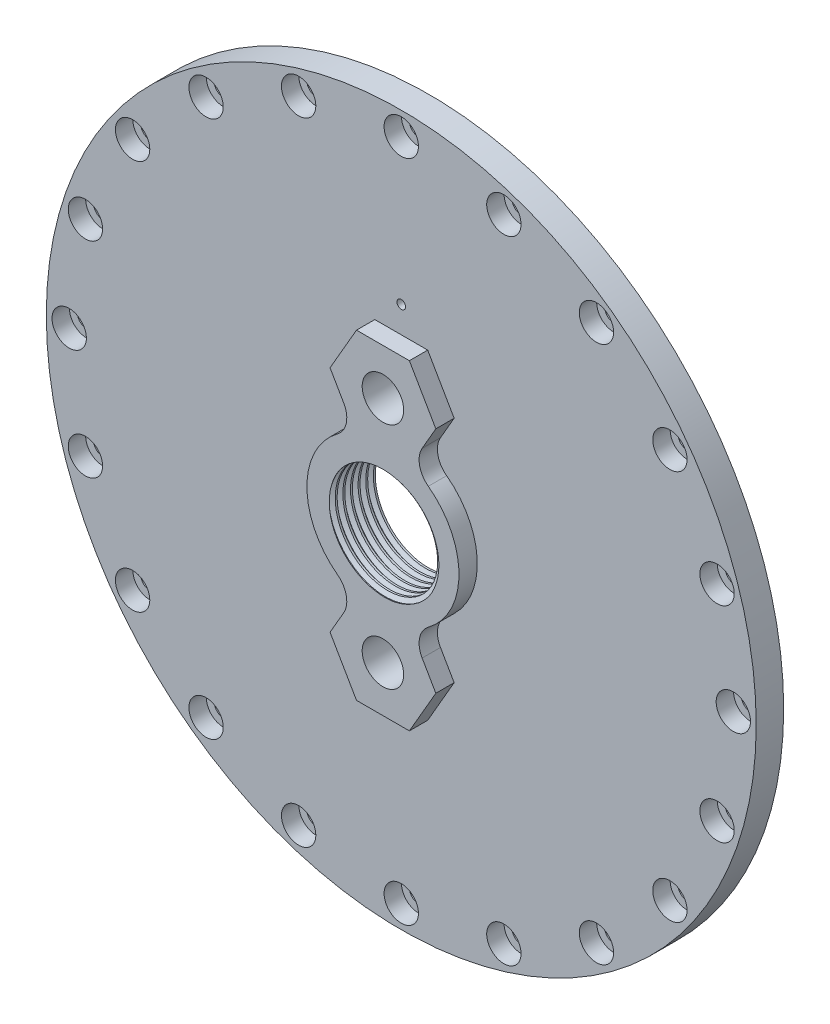
SolidWorks part; units mm, degrees
ref_plane "Front Plane" through (0, 0, 0) normal (0, 0, 1) x (1, 0, 0)
ref_plane "Top Plane" through (0, 0, 0) normal (0, 1, 0) x (1, 0, 0)
ref_plane "Right Plane" through (0, 0, 0) normal (1, 0, 0) x (0, 0, -1)
sketch "Sketch1" plane through (0, 0, 0) normal (1, 0, 0) x (0, 0, -1)
  line L0 (0, 21.082) -> (0, 98.425)
  line L1 (0, 98.425) -> (7.62, 98.425)
  line L2 (7.62, 98.425) -> (7.62, 88.6333)
  line L3 (7.62, 83.82) -> (5.08, 83.82)
  line L4 (5.08, 83.82) -> (5.08, 56.8325)
  line L5 (5.08, 56.8325) -> (7.62, 56.8325)
  line L6 (7.62, 56.8325) -> (7.62, 53.0225)
  line L7 (7.62, 14.732) -> (-5.08, 14.732)
  line L8 (-5.08, 14.732) -> (-5.08, 21.082)
  line L9 (-5.08, 21.082) -> (0, 21.082)
  line L10 (0, 0) -> (59.2702, 0) construction
  line L12 (7.62, 49.6951) -> (6.2992, 49.6951)
  line L14 (7.62, 47.0535) -> (6.2992, 47.0535)
  line L15 (6.2992, 49.6951) -> (6.2992, 47.0535)
  line L20 (7.62, 47.0535) -> (7.62, 46.0375)
  line L21 (7.62, 85.1027) -> (7.62, 83.82)
  line L22 (7.62, 50.4825) -> (7.62, 49.6951)
  line L23 (7.62, 21.59) -> (7.62, 14.732)
  line L24 (7.62, 46.0375) -> (5.08, 46.0375)
  line L26 (7.62, 21.59) -> (5.08, 21.59)
  line L27 (5.08, 46.0375) -> (5.08, 21.59)
  line L28 (7.62, 53.0225) -> (6.35, 53.0225)
  line L32 (7.62, 50.4825) -> (6.35, 50.4825)
  line L33 (6.35, 53.0225) -> (6.35, 50.4825)
  line L35 (7.62, 88.6333) -> (5.6642, 88.6333)
  line L37 (7.62, 85.1027) -> (5.6642, 85.1027)
  line L38 (5.6642, 88.6333) -> (5.6642, 85.1027)
  point P19 (6.35, 51.7525)
  point P22 (6.2992, 48.3743)
  point P31 (5.6642, 86.868)
  dimension "D1" = 196.85
  dimension "D2" = 2.54
  dimension "D3" = 7.62
  dimension "D4" = 2.54
  dimension "D5" = 113.665
  dimension "D6" = 12.7
  dimension "D7" = 29.464
  dimension "D8" = 6.35
  dimension "D9" = 2.6416
  dimension "D10" = 96.7486
  dimension "D11" = 1.3208
  dimension "D12" = 167.64
  dimension "D13" = 92.075
  dimension "D14" = 43.18
  dimension "D15" = 1.27
  dimension "D16" = 2.54
  dimension "D17" = 103.505
  dimension "D18" = 1.9558
  dimension "D19" = 3.5306
  dimension "D20" = 173.736
revolve "Revolve1" add sketch "Sketch1" angle 360 about L10 region at (0, 54.7882, -2.7116)
thread "Thread1" pitch 2.1167 method cut profile "Thread Profile1" start angle 0, offset 4.318, length 0, pitch 2.1167, diameter 29.464
ref_plane "Plane1" through (-14.732, 0, 9.398) normal (0, -1, 0) x (-1, 0, 0)
sketch "Thread Profile1" plane through (-14.732, 0, 9.398) normal (0, -1, 0) x (-1, 0, 0)
  line L0 (0, 0) -> (0, 2.1167) construction
  line L1 (0, 0) -> (1.1457, 0.6615)
  line L2 (1.1457, 0.6615) -> (1.1457, 0.926)
  line L3 (1.1457, 0.926) -> (0, 1.5875)
  line L4 (1.1457, 0.7937) -> (0, 0.7937) construction
  line L11 (0, 0) -> (0, 1.5875)
  point P2 (0, 0)
  dimension "Pitch" = 2.1167
  dimension "Profile_Angle" = 60
  dimension "Profile_Land" = 0.2646
  dimension "Profile_Height" = 1.1457
sketch "Sketch15" plane through (0, 0, 0) normal (0, 0, 1) x (1, 0, 0)
  line L10 (0, 0) -> (104.8126, 0) construction
  line L11 (7.3323, 19.05) -> (14.6647, 31.75)
  line L12 (14.6647, 31.75) -> (7.3323, 44.45)
  line L13 (7.3323, 44.45) -> (-7.3323, 44.45)
  line L14 (-7.3323, 44.45) -> (-14.6647, 31.75)
  line L15 (-14.6647, 31.75) -> (-7.3323, 19.05)
  line L16 (-7.3323, 19.05) -> (7.3323, 19.05)
  line L17 (-7.3323, -19.05) -> (7.3323, -19.05)
  line L18 (-14.6647, -31.75) -> (-7.3323, -19.05)
  line L19 (-7.3323, -44.45) -> (-14.6647, -31.75)
  line L20 (7.3323, -44.45) -> (-7.3323, -44.45)
  line L21 (14.6647, -31.75) -> (7.3323, -44.45)
  line L22 (7.3323, -19.05) -> (14.6647, -31.75)
  circle A8 centre (0, 31.75) radius 12.7 construction
  circle A9 centre (0, -31.75) radius 12.7 construction
  dimension "D2" = 63.5
  dimension "D1" = 25.4
extrude "Boss-Extrude1" add sketch "Sketch15" along normal up to surface (5.08 mm away) up to face at (21.082, 0, 5.08)
hole_wizard "1/2-20 Tapped Hole2" positions "Sketch20" profile "Sketch17" tap size "1/2-20" standard "ANSI Inch" end condition through all
sketch "Sketch20" plane through (0, 0, 5.08) normal (0, 0, 1) x (1, 0, 0)
  point P9 (0, 31.75)
  point P16 (0, -31.75)
sketch "Sketch17" plane through (0, 31.75, 5.08) normal (1, 0, 0) x (0, -1, 0)
  line L0 (0, 0) -> (0, 13.4424)
  line L1 (0, 13.4424) -> (5.7544, 13.4424)
  line L2 (5.7544, 13.4424) -> (5.7544, 0)
  line L5 (5.7544, 0) -> (0, 0)
  line L11 (0, -6.35) -> (0, 107.95) construction
  dimension "Thru Tap Drill Dia." = 11.5087
  dimension "Thru Tap Drill Depth" = 13.4424
cosmetic thread "Hole Thread3"
cosmetic thread "Hole Thread4"
hole_wizard "CBORE for #10 Socket Head Cap Screw1" positions "Sketch19" profile "Sketch9" counterbore size "#10" standard "ANSI Inch" end condition up to next
sketch "Sketch19" plane through (0, 0, 0) normal (0, 0, 1) x (1, 0, 0)
  circle A0 centre (0, 0) radius 92.075 construction
  point P0 (0, 92.075)
  point P16 (28.4527, 87.5685)
  point P17 (54.1203, 74.4902)
  point P18 (74.4902, 54.1203)
  point P19 (87.5685, 28.4527)
  point P20 (92.075, 0)
  point P21 (87.5685, -28.4527)
  point P22 (74.4902, -54.1203)
  point P23 (54.1203, -74.4902)
  point P24 (28.4527, -87.5685)
  point P25 (0, -92.075)
  point P26 (-28.4527, -87.5685)
  point P27 (-54.1203, -74.4902)
  point P28 (-74.4902, -54.1203)
  point P29 (-87.5685, -28.4527)
  point P30 (-92.075, 0)
  point P31 (-87.5685, 28.4527)
  point P32 (-74.4902, 54.1203)
  point P33 (-54.1203, 74.4902)
  point P34 (-28.4527, 87.5685)
  dimension "D1" = 184.15
  dimension "D2" = 20
sketch "Sketch9" plane through (0, 92.075, 0) normal (1, 0, 0) x (0, -1, 0)
  line L0 (0, 0) -> (0, 7.62)
  line L1 (0, 7.62) -> (2.5527, 7.62)
  line L3 (2.5527, 7.62) -> (2.5527, 4.826)
  line L4 (2.5527, 4.826) -> (4.7625, 4.826)
  line L5 (4.7625, 4.826) -> (4.7625, 0)
  line L7 (4.7625, 0) -> (0, 0)
  line L11 (0, -6.35) -> (0, 107.95) construction
  dimension "Thru Hole Dia." = 5.1054
  dimension "Thru Hole Depth" = 7.62
  dimension "C'Bore Dia." = 9.525
  dimension "C'Bore Depth" = 4.826
fillet "Fillet1" radius 6.35 4 edges at (-7.6711, 19.6368, 2.54) (-7.6711, -19.6368, 2.54) (7.6711, -19.6368, 2.54) (7.6711, 19.6368, 2.54)
hole_wizard "3/32 (0.09375) Dowel Hole1" positions "Sketch23" profile "Sketch22" hole size "3/32" standard "ANSI Inch" end condition up to next
sketch "Sketch23" plane through (0, 0, -6.35) normal (0, 0, -1) x (-1, 0, 0)
  line L0 (0, 50.4825) -> (0, 53.0225) construction
  circle A1 centre (0, 0) radius 50.4825 construction
  circle A2 centre (0, 0) radius 53.0225 construction
  point P0 (0, 51.7525)
  point P15 (0, 51.7525)
sketch "Sketch22" plane through (0, 51.7525, -6.35) normal (1, 0, 0) x (0, 1, 0)
  line L0 (0, 0) -> (0, 6.35)
  line L1 (0, 6.35) -> (1.1906, 6.35)
  line L2 (1.1906, 6.35) -> (1.1906, 0)
  line L5 (1.1906, 0) -> (0, 0)
  line L11 (0, -6.35) -> (0, 107.95) construction
  dimension "Thru Hole Dia." = 2.3812
  dimension "Thru Hole Depth" = 6.35
